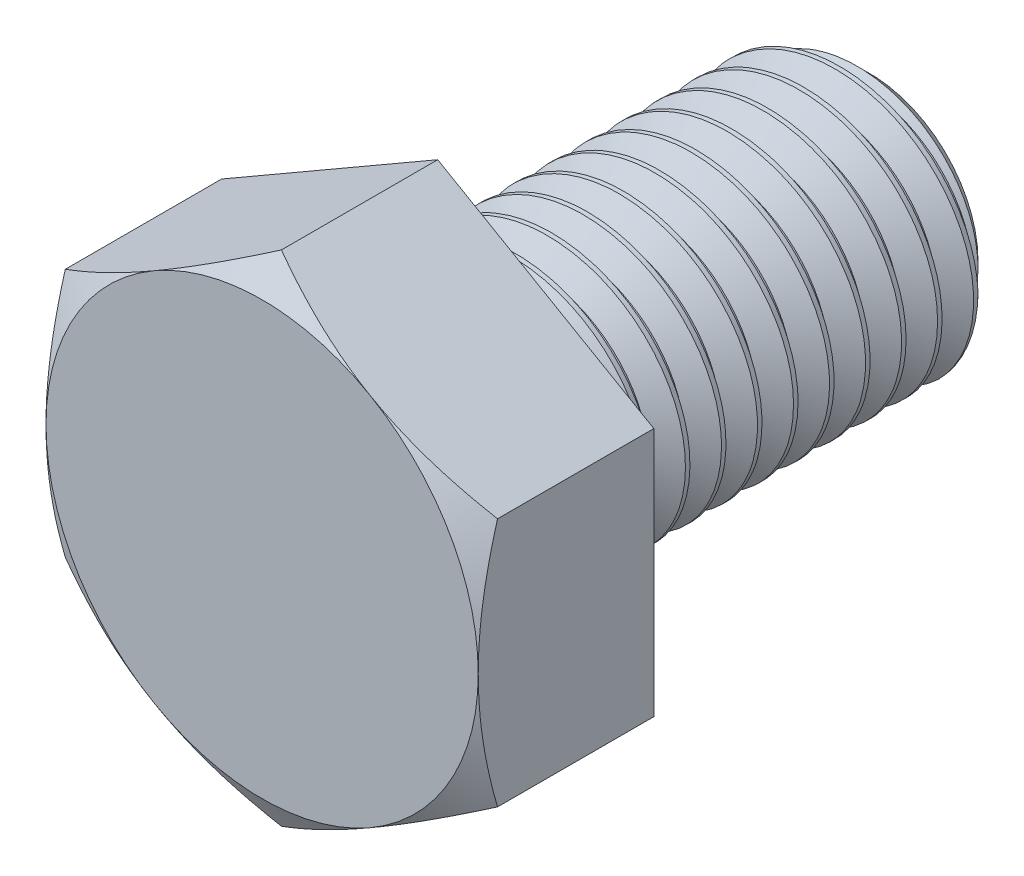
SolidWorks part; units mm, degrees
ref_plane "Front Plane" through (0, 0, 0) normal (0, 0, 1) x (1, 0, 0)
ref_plane "Top Plane" through (0, 0, 0) normal (0, 1, 0) x (1, 0, 0)
ref_plane "Right Plane" through (0, 0, 0) normal (1, 0, 0) x (0, 0, -1)
sketch "Sketch1" plane through (0, 0, 0) normal (1, 0, 0) x (0, 0, -1)
  line L0 (0, 0) -> (12.7, 0) construction
  line L1 (12.7, 3.9688) -> (12.7, -3.9688) construction
  line L2 (0, 6.35) -> (0, -6.35) construction
  line L3 (0, 0) -> (-5.1594, 0) construction
  line L4 (-5.1594, 6.35) -> (-5.1594, -6.35) construction
  line L5 (12.6339, 4.0833) -> (13.6922, 4.0833) construction
  line L6 (13.6922, 4.0833) -> (13.163, 3.1668) construction
  line L7 (13.163, 3.1668) -> (12.6339, 4.0833) construction
  line L8 (12.6669, 4.026) -> (13.6591, 4.026) construction
  line L9 (12.7, 3.9688) -> (13.626, 3.9688) construction
  line L10 (13.0969, 3.2813) -> (13.2292, 3.2813) construction
  line L11 (13.163, 4.0833) -> (13.163, 3.9688) construction
  line L12 (13.163, 3.2813) -> (13.163, 3.1668) construction
  point P5 (12.7, 0)
  point P9 (0, 0)
  point P13 (-5.1594, 0)
  point P18 (10.0542, -3.9688)
  point P25 (13.163, 4.026)
  dimension "Length" = 12.7
  dimension "Thread OD" = 7.9375
  dimension "Hex Width" = 12.7
  dimension "Hex Height" = 5.1594
  dimension "D1" = 60
  dimension "Pitch" = 1.0583
  dimension "D2" = 0.1323
  dimension "D3" = 2.6458
sketch "Sketch2" plane through (0, 0, 0) normal (1, 0, 0) x (0, 0, -1)
  line L0 (0, 0) -> (12.7, 0)
  line L1 (0, 6.35) -> (0, -6.35) construction
  line L2 (12.7, 0) -> (12.7, 3.9688)
  line L3 (12.7, 3.9688) -> (0, 3.9687)
  line L4 (0, 3.9687) -> (0, 0)
revolve "Revolve1" add sketch "Sketch2" angle 360 about L0
sketch "Sketch3" plane through (0, 0, 0) normal (0, 0, 1) x (1, 0, 0)
  line L1 (0, 7.3323) -> (-6.35, 3.6662)
  line L2 (-6.35, 3.6662) -> (-6.35, -3.6662)
  line L3 (-6.35, -3.6662) -> (0, -7.3323)
  line L4 (0, -7.3323) -> (6.35, -3.6662)
  line L5 (6.35, -3.6662) -> (6.35, 3.6662)
  line L6 (6.35, 3.6662) -> (0, 7.3323)
  circle A0 centre (0, 0) radius 6.35 construction
extrude "Boss-Extrude1" add sketch "Sketch3" along normal up to vertex (5.1594 mm away) up to point (0, 0, 5.1594)
chamfer "Chamfer1" distance 0.7938 angle 45 1 edges at (3.9688, 0, -12.7)
sketch "Sketch4" plane through (0, 0, 5.1594) normal (0, 0, 1) x (1, 0, 0)
  circle A0 centre (0, 0) radius 6.35
extrude "Cut-Extrude1" cut sketch "Sketch4" against normal through all draft 60 flip side to cut
ref_axis "Center Axis 1" through (0, 0, -68.7678) along (0, 0, 1)
split "Split1" bodies to split 106 resulting bodies 107 108 split by face at (3.9687, 0, 0)
sketch "Sketch5" plane through (0, 0, 0) normal (1, 0, 0) x (0, 0, -1)
  line L0 (12.6669, 4.026) -> (13.6591, 4.026)
  line L1 (12.6669, 4.026) -> (13.0969, 3.2813)
  line L2 (13.0969, 3.2813) -> (13.2292, 3.2813)
  line L3 (13.6591, 4.026) -> (13.2292, 3.2813)
sketch "Sketch6" plane through (0, 0, -12.7) normal (0, 0, -1) x (-1, 0, 0)
  circle A0 centre (0, 0) radius 3.9688
curve "Helix/Spiral1" pitch 1.0583 height 13.7583 radius 3.9688 centre (0, 0, -12.7) axis (0, 0, 1) start towards (0, 1, 0)
sweep "Cut-Sweep1" cut profiles "Sketch5" path "Helix/Spiral1" align with end faces yes
combine bodies "Combine1" operation type add bodies to combine 108 109
equation "\"D2@Sketch1\"=\"Pitch@Sketch1\"/8"
equation "\"D1@Chamfer1\"=\"Pitch@Sketch1\"*.75"
equation "\"D4@Helix/Spiral1\"=\"Pitch@Sketch1\""
equation "\"D3@Helix/Spiral1\"=\"Length@Sketch1\"+\"Pitch@Sketch1\""
equation "\"D3@Sketch1\"=\"Pitch@Sketch1\"*2.5"
